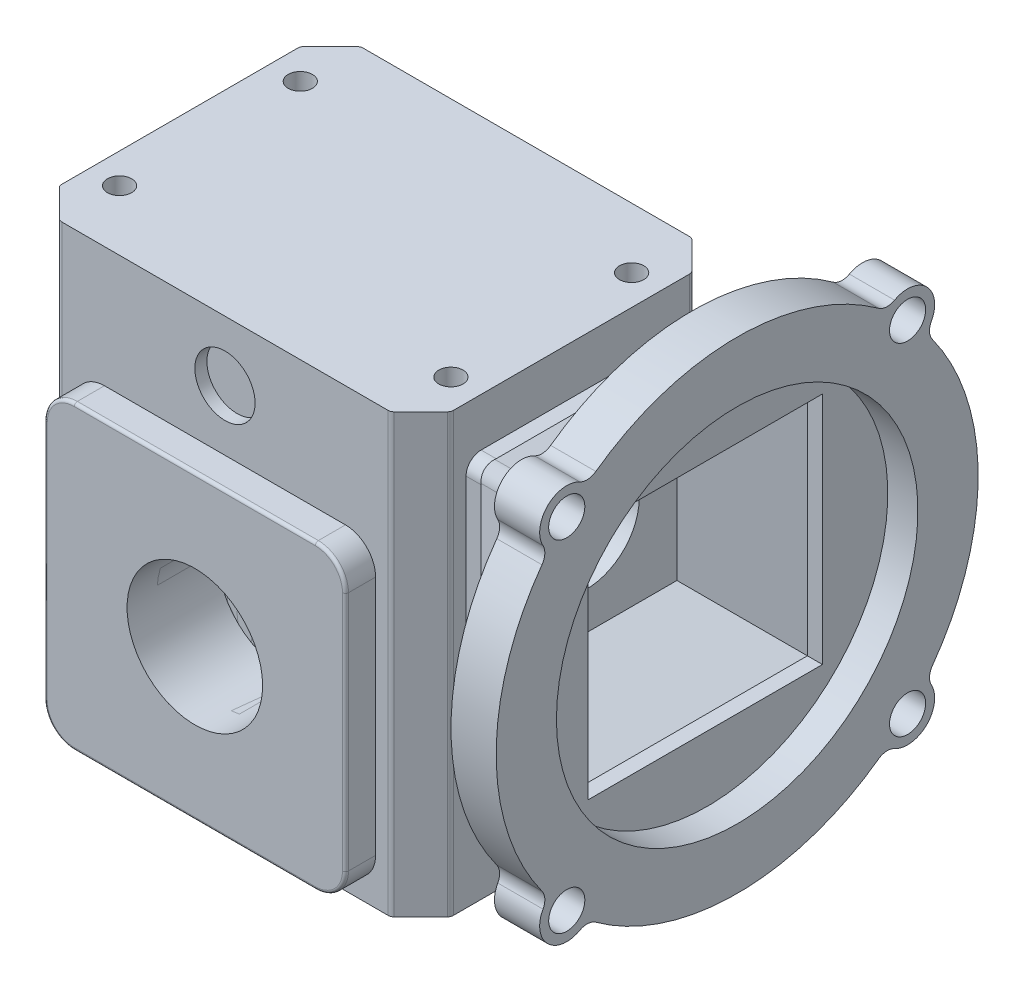
SolidWorks part; units mm, degrees
ref_plane "Front Plane" through (0, 0, 0) normal (0, 0, 1) x (1, 0, 0)
ref_plane "Top Plane" through (0, 0, 0) normal (0, 1, 0) x (1, 0, 0)
ref_plane "Right Plane" through (0, 0, 0) normal (1, 0, 0) x (0, 0, -1)
sketch "Sketch1" plane through (0, 0, 0) normal (0, 1, 0) x (1, 0, 0)
  line L1 (-41.275, -31.75) -> (41.275, -31.75)
  line L2 (-41.275, -31.75) -> (-41.275, 31.75)
  line L3 (-41.275, 31.75) -> (41.275, 31.75)
  line L4 (41.275, -31.75) -> (41.275, 31.75)
  line L5 (-41.275, -31.75) -> (41.275, 31.75) construction
  line L6 (-41.275, 31.75) -> (41.275, -31.75) construction
  point P0 (0, 0)
  dimension "D1" = 82.55
  dimension "D2" = 63.5
extrude "Boss-Extrude1" add sketch "Sketch1" along normal mid plane 92.202
chamfer "Chamfer1" distance 6.35 distance2 6.35 4 edges at (41.275, 0, -31.75) (-41.275, 0, -31.75) (-41.275, 0, 31.75) (41.275, 0, 31.75)
sketch "Sketch2" plane through (0, 0, 31.75) normal (0, 0, 1) x (1, 0, 0)
  line L0 (-34.925, -46.101) -> (34.925, -46.101) construction
  line L1 (-31.75, 20.701) -> (31.75, 20.701)
  line L2 (-31.75, 20.701) -> (-31.75, -42.799)
  line L3 (-31.75, -42.799) -> (31.75, -42.799)
  line L4 (31.75, 20.701) -> (31.75, -42.799)
  dimension "D1" = 63.5
  dimension "D2" = 63.5
  dimension "D3" = 31.75
  dimension "D4" = 3.302
extrude "Boss-Extrude2" add sketch "Sketch2" along normal blind 6.35 and the other way blind 69.85 separate body
fillet "Fillet1" radius 6.35 4 edges at (-31.75, -42.799, 0) (31.75, -42.799, 0) (31.75, 20.701, 0) (-31.75, 20.701, 0)
fillet "Fillet2" radius 0.635 16 edges at (-29.8901, 18.8411, -38.1) (0, 20.701, -38.1) (29.8901, 18.8411, -38.1) (31.75, -11.049, -38.1) (29.8901, -40.9391, -38.1) (0, -42.799, -38.1) (-29.8901, -40.9391, -38.1) (29.8901, 18.8411, 38.1) (31.75, -11.049, 38.1) (29.8901, -40.9391, 38.1) (0, -42.799, 38.1) (-29.8901, -40.9391, 38.1) (-31.75, -11.049, 38.1) (-29.8901, 18.8411, 38.1) (-31.75, -11.049, -38.1) (0, 20.701, 38.1)
fillet "Fillet3" radius 1.27 8 edges at (34.925, 0, 31.75) (41.275, 0, 25.4) (41.275, 0, -25.4) (34.925, 0, -31.75) (-34.925, 0, -31.75) (-41.275, 0, -25.4) (-41.275, 0, 25.4) (-34.925, 0, 31.75)
sketch "Sketch3" plane through (0, 0, 38.1) normal (0, 0, 1) x (1, 0, 0)
  line L0 (-31.115, -42.164) -> (31.115, 20.066) construction
  line L1 (-31.115, 20.066) -> (31.115, -42.164) construction
  circle A0 centre (0, -11.049) radius 14.2875
  dimension "D1" = 28.575
extrude "Cut-Extrude1" cut sketch "Sketch3" against normal blind 19.05
sketch "Sketch4" plane through (41.275, 0, 0) normal (1, 0, 0) x (0, 0, -1)
  line L0 (24.8739, 46.101) -> (-24.8739, 46.101) construction
  line L1 (-22.2069, 35.941) -> (22.2431, 35.941)
  line L2 (-22.2069, 35.941) -> (-22.2069, -8.509)
  line L3 (-22.2069, -8.509) -> (22.2431, -8.509)
  line L4 (22.2431, 35.941) -> (22.2431, -8.509)
  line L5 (-24.8739, 46.101) -> (24.8739, 46.101) construction
  line L8 (-24.8739, 46.101) -> (-24.8739, -46.101) construction
  dimension "D1" = 10.16
  dimension "D2" = 44.45
  dimension "D3" = 44.45
  dimension "D4" = 2.667
extrude "Boss-Extrude3" add sketch "Sketch4" along normal blind 3.175
sketch "Sketch5" plane through (0, 0, 0) normal (0, 0, 1) x (1, 0, 0)
  line L0 (44.45, 35.941) -> (66.675, 45.466)
  line L1 (66.675, 45.466) -> (66.675, 42.291)
  line L2 (66.675, 42.291) -> (44.45, 32.766)
  line L3 (44.45, 35.941) -> (44.45, -8.509) construction
  line L4 (44.45, 35.941) -> (41.275, 35.941) construction
  line L5 (41.275, 35.941) -> (41.275, -8.509) construction
  line L6 (44.45, 35.941) -> (44.45, 32.766)
  dimension "D1" = 3.175
  dimension "D2" = 9.525
  dimension "D3" = 25.4
sketch "Sketch6" plane through (44.45, 0, 0) normal (1, 0, 0) x (0, 0, -1)
  line L1 (-22.2069, 35.941) -> (22.2431, 35.941)
  line L2 (-22.2069, 35.941) -> (-22.2069, -8.509)
  line L3 (-22.2069, -8.509) -> (22.2431, -8.509)
  line L4 (22.2431, 35.941) -> (22.2431, -8.509)
sweep "Sweep1" add profiles "Sketch5" path "Sketch6"
fillet "Fillet4" radius 3.175 8 edges at (55.5625, -13.2715, -27.0056) (42.8625, -8.509, -22.2431) (55.5625, 40.7035, -27.0056) (42.8625, 35.941, -22.2431) (42.8625, 35.941, 22.2069) (42.8625, -8.509, 22.2069) (55.5625, -13.2715, 26.9694) (55.5625, 40.7035, 26.9694)
sketch "Sketch7" plane through (66.675, 0, 0) normal (1, 0, 0) x (0, 0, -1)
  line L0 (28.5931, 42.291) -> (-28.5569, -14.859) construction
  line L1 (-28.5569, 42.291) -> (28.5931, -14.859) construction
  line L3 (-25.0454, 38.7795) -> (24.346, 38.7795)
  line L4 (-25.0454, 38.7795) -> (-25.0454, -10.6119)
  line L5 (-25.0454, -10.6119) -> (24.346, -10.6119)
  line L6 (24.346, 38.7795) -> (24.346, -10.6119)
  circle A0 centre (0.0181, 13.716) radius 50.8
  circle A1 centre (0.0181, 13.716) radius 38.1
  line M3 (-28.8137, -18.034) -> (28.8498, -18.034)
  line M5 (31.7681, -15.1157) -> (31.7681, 42.5477)
  line M7 (28.8498, 45.466) -> (-28.8137, 45.466)
  line M9 (-31.7319, 42.5477) -> (-31.7319, -15.1157)
  line M11 (-28.5569, -14.859) -> (-28.5569, 42.291)
  line M12 (-28.5569, 42.291) -> (28.5931, 42.291)
  line M13 (28.5931, 42.291) -> (28.5931, -14.859)
  line M14 (28.5931, -14.859) -> (-28.5569, -14.859)
  dimension "D1" = 76.2
  dimension "D2" = 101.6
  dimension "D3" = 69.85
extrude "Boss-Extrude4" add sketch "Sketch7" along normal blind 3.175 contours A1 M7 | A1 M9 | A1 M5 | A1 M3 | A1 M14 M3 | A1 L3 L6 L5 L4 M13 M12 M11 M14 | A1 M11 M9 | A1 M12 M7 | A1 M5 M13 region at (66.675, 13.716, -34.3271) region at (66.675, 13.716, -30.1335) region at (66.675, 13.716, -27.7848) region at (66.675, 43.8315, -0.0181) region at (66.675, -16.3995, -0.0181) region at (66.675, 48.0251, -0.0181) region at (66.675, -20.5931, -0.0181) region at (66.675, 13.716, 30.0974) region at (66.675, 13.716, 34.291)
sketch "Sketch8" plane through (66.675, 0, 0) normal (1, 0, 0) x (0, 0, -1)
  circle A0 centre (0.0181, 13.716) radius 38.1
  circle A1 centre (0.0181, 13.716) radius 50.8
  dimension "D1" = 101.6
extrude "Boss-Extrude5" add sketch "Sketch8" along normal blind 9.525
sketch "Sketch12" plane through (76.2, 0, 0) normal (1, 0, 0) x (0, 0, -1)
  line L0 (0.0181, 13.716) -> (-42.6924, 56.4265) construction
  circle A0 centre (0.0181, 13.716) radius 54.61 construction
  circle A1 centre (0.0181, 13.716) radius 50.8 construction
  circle A2 centre (-35.903, 49.637) radius 3.81
  circle A3 centre (35.9391, 49.637) radius 3.81
  circle A4 centre (35.9391, -22.205) radius 3.81
  circle A5 centre (-35.903, -22.205) radius 3.81
  circle A6 centre (-35.903, 49.637) radius 5.715
  circle A7 centre (-35.903, -22.205) radius 5.715
  circle A8 centre (35.9391, -22.205) radius 5.715
  circle A9 centre (35.9391, 49.637) radius 5.715
  point P15 (0.0181, 13.716)
  dimension "D1" = 109.22
  dimension "D2" = 101.6
  dimension "D3" = 11.43
  dimension "D4" = 11.43
  dimension "D5" = 11.43
  dimension "D6" = 11.43
extrude "Boss-Extrude6" add sketch "Sketch12" against normal blind 9.525
sketch "Sketch13" plane through (76.2, 0, 0) normal (1, 0, 0) x (0, 0, -1)
  circle A0 centre (-35.903, 49.637) radius 3.81
  arc A1 (-33.1098, 52.2282) -> (-38.4941, 46.8438) centre (0.0181, 13.716) ccw construction
  circle A2 centre (35.9391, 49.637) radius 3.81
  arc A3 (38.5302, 46.8438) -> (33.1459, 52.2282) centre (0.0181, 13.716) ccw construction
  circle A4 centre (35.9391, -22.205) radius 3.81
  arc A5 (33.1459, -24.7962) -> (38.5302, -19.4118) centre (0.0181, 13.716) ccw construction
  circle A6 centre (-35.903, -22.205) radius 3.81
  arc A7 (-38.4941, -19.4118) -> (-33.1098, -24.7962) centre (0.0181, 13.716) ccw construction
extrude "Cut-Extrude2" cut sketch "Sketch13" against normal blind 9.525
fillet "Fillet5" radius 3.175 8 edges at (71.4375, -17.943, 39.7104) (71.4375, -26.0124, 31.6409) (71.4375, -26.0124, -31.677) (71.4375, -17.943, -39.7465) (71.4375, 45.375, -39.7465) (71.4375, 53.4444, -31.677) (71.4375, 53.4444, 31.6409) (71.4375, 45.375, 39.7104)
sketch "Sketch14" plane through (44.45, 0, 0) normal (1, 0, 0) x (0, 0, -1)
  line L0 (19.0681, 32.766) -> (-19.0319, -5.334) construction
  line L1 (-19.0319, 32.766) -> (19.0681, -5.334) construction
  circle A0 centre (0.0181, 13.716) radius 11.1125
  dimension "D1" = 22.225
extrude "Cut-Extrude3" cut sketch "Sketch14" against normal blind 6.35
sketch "Sketch15" plane through (0, 46.101, 0) normal (0, 1, 0) x (1, 0, 0)
  line L0 (-34.3989, -31.75) -> (34.3989, -31.75) construction
  line L1 (-41.275, 24.8739) -> (-41.275, -24.8739) construction
  line L2 (-41.275, 0) -> (41.275, 0) construction
  line L3 (41.275, -24.8739) -> (41.275, 24.8739) construction
  line L4 (0, 31.75) -> (0, -31.75) construction
  line L5 (34.3989, 31.75) -> (-34.3989, 31.75) construction
  circle A0 centre (-34.925, -19.05) radius 3.449
  circle A1 centre (34.925, -19.05) radius 3.449
  circle A2 centre (34.925, 19.05) radius 3.449
  circle A3 centre (-34.925, 19.05) radius 3.449
  dimension "D1" = 12.7
  dimension "D2" = 6.35
hole_wizard "Tap Drill for 1/4-20 Tap1" positions "Sketch17" profile "Sketch16" hole size "1/4-20" standard "ANSI Inch"
sketch "Sketch17" plane through (0, 46.101, 0) normal (0, 1, 0) x (1, 0, 0)
  point P0 (-34.925, 19.05)
  point P3 (-34.925, -19.05)
  point P6 (34.925, 19.05)
  point P9 (34.925, -19.05)
sketch "Sketch16" plane through (-34.925, 46.101, -19.05) normal (1, 0, 0) x (0, 0, 1)
  line L0 (0, 0) -> (0, 17.5358)
  line L1 (0, 17.5358) -> (2.5527, 16.002)
  line L2 (2.5527, 16.002) -> (2.5527, 0)
  line L5 (2.5527, 0) -> (0, 0)
  line L10 (0, 17.5358) -> (-2.5527, 16.002) construction
  line L11 (0, -6.35) -> (0, 107.95) construction
  dimension "Hole Dia." = 5.1054
  dimension "Hole Depth" = 16.002
  dimension "Drill Angle" = 118
sketch "Sketch18" plane through (0, 0, 31.75) normal (0, 0, 1) x (1, 0, 0)
  line L0 (34.3989, 46.101) -> (-34.3989, 46.101) construction
  circle A0 centre (0, 33.401) radius 6.35
  point P2 (0, 46.101)
  dimension "D1" = 12.7
  dimension "D2" = 12.7
extrude "Cut-Extrude4" cut sketch "Sketch18" against normal blind 2.54
sketch "Sketch19" plane through (0, -46.101, 0) normal (0, -1, 0) x (1, 0, 0)
  line L0 (-41.275, -24.8739) -> (-41.275, 24.8739) construction
  circle A0 centre (-34.925, -19.05) radius 3.175
  circle A1 centre (34.925, -19.05) radius 3.175
  circle A2 centre (34.925, 19.05) radius 3.175
  circle A3 centre (-34.925, 19.05) radius 3.175
  dimension "D1" = 6.35
  dimension "D3" = 6.35
  dimension "D2" = 12.7
extrude "Cut-Extrude5" cut sketch "Sketch19" against normal blind 12.7
